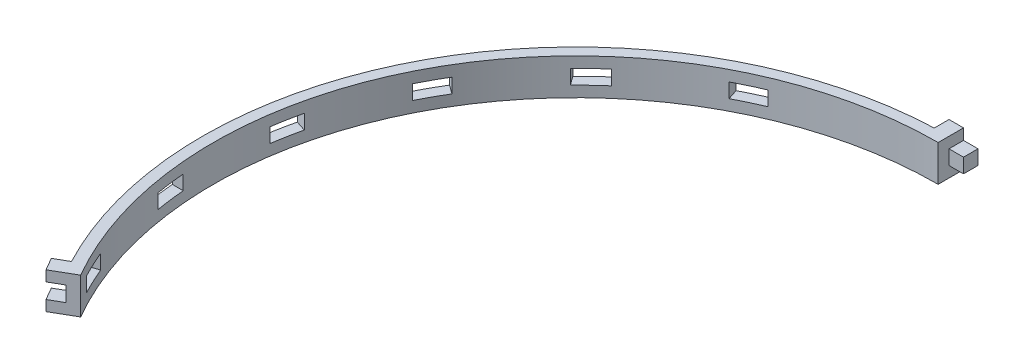
SolidWorks part; units mm, degrees
note: '?' marks a value the reader was unsure of.
ref_plane "Front Plane" through (0, 0, 0) normal (0, 0, 1) x (1, 0, 0)
ref_plane "Top Plane" through (0, 0, 0) normal (0, 1, 0) x (1, 0, 0)
ref_plane "Right Plane" through (0, 0, 0) normal (1, 0, 0) x (0, 0, -1)
sketch "Sketch1" plane through (0, 0, 0) normal (0, 1, 0) x (1, 0, 0)
  line L0 (103, 0) -> (100, 0) construction
  line L1 (0, 103) -> (0, -103)
  line L6 (0, 0) -> (-215.0076, 0) construction
  line L7 (0, 0) -> (-89.2006, -51.5)
  line L17 (0, 103) -> (0, 100)
  line L18 (0, 101) -> (-4, 101)
  line L19 (0, 101) -> (0, 107)
  line L20 (0, 107) -> (-4, 107)
  line L21 (-4, 101) -> (-4, 107)
  line L22 (-87.4686, -50.5) -> (-92.6647, -53.5)
  line L23 (-92.6647, -53.5) -> (-94.6647, -50.0359)
  line L24 (-94.6647, -50.0359) -> (-89.4686, -47.0359)
  line L25 (-89.4686, -47.0359) -> (-87.4686, -50.5)
  circle A0 centre (0, 0) radius 100
  circle A1 centre (0, 0) radius 103
  dimension "D1" = 200
  dimension "D2" = 3
  dimension "D3" = 120
  dimension "D4" = 4
  dimension "D5" = 4
  dimension "D6" = 4
  dimension "D7" = 4
  dimension "D8" = 101
  dimension "D9" = 101
extrude "Boss-Extrude1" add sketch "Sketch1" along normal blind 10
ref_axis "Axis1" through (0, 10, 0) along (0, -1, 0)?
sketch "Sketch2" plane through (-92.6647, 0, 53.5) normal (-0.866, 0, 0.5) x (0.5, 0, 0.866)
  line L1 (-4, 7.1) -> (4, 7.1)
  line L2 (-4, 7.1) -> (-4, 2.9)
  line L3 (-4, 2.9) -> (4, 2.9)
  line L4 (4, 7.1) -> (4, 2.9)
  line L5 (-4, 10) -> (-4, 0) construction
  point P6 (-4, 5)
  point P7 (-4, 5)
  dimension "D1" = 4.2
  dimension "D2" = 8
extrude "Cut-Extrude1" cut sketch "Sketch2" against normal blind 4
sketch "Sketch3" plane through (0, 0, -107) normal (0, 0, -1) x (-1, 0, 0)
  line L1 (4, 3) -> (-4, 3)
  line L2 (4, 3) -> (4, 7)
  line L3 (4, 7) -> (-4, 7)
  line L4 (-4, 3) -> (-4, 7)
  line L5 (4, 10) -> (4, 0) construction
  point P6 (4, 5)
  point P7 (4, 5)
  dimension "D2" = 8
  dimension "D1" = 4
extrude "Boss-Extrude2" add sketch "Sketch3" against normal blind 4 contours L2 L1 L4 L3
sketch "Sketch4" plane through (0, 0, 0) normal (1, 0, 0) x (0, 0, -1)
  line L0 (-47.997, 0) -> (102.9223, 0) construction
  line L1 (-8.6723, 7) -> (-16.6723, 7)
  line L2 (-8.6723, 7) -> (-8.6723, 3)
  line L3 (-8.6723, 3) -> (-16.6723, 3)
  line L4 (-16.6723, 7) -> (-16.6723, 3)
  line L5 (102.9223, 10) -> (-47.997, 10) construction
  dimension "D1" = 3
  dimension "D2" = 3
  dimension "D3" = 8
extrude "Cut-Extrude2" cut sketch "Sketch4" against normal through all
pattern_circular "CirPattern4" count 5 every 18 about axis through (0, 0, 0) along (0, 1, 0) of "Cut-Extrude2"
equation "\"key_height\"= 4mm"
equation "\"slot_height\"= \"key_height\" + 0.2mm"
equation "\"D1@Sketch2\"=\"slot_height\""
equation "\"D1@Sketch3\"=\"key_height\""
